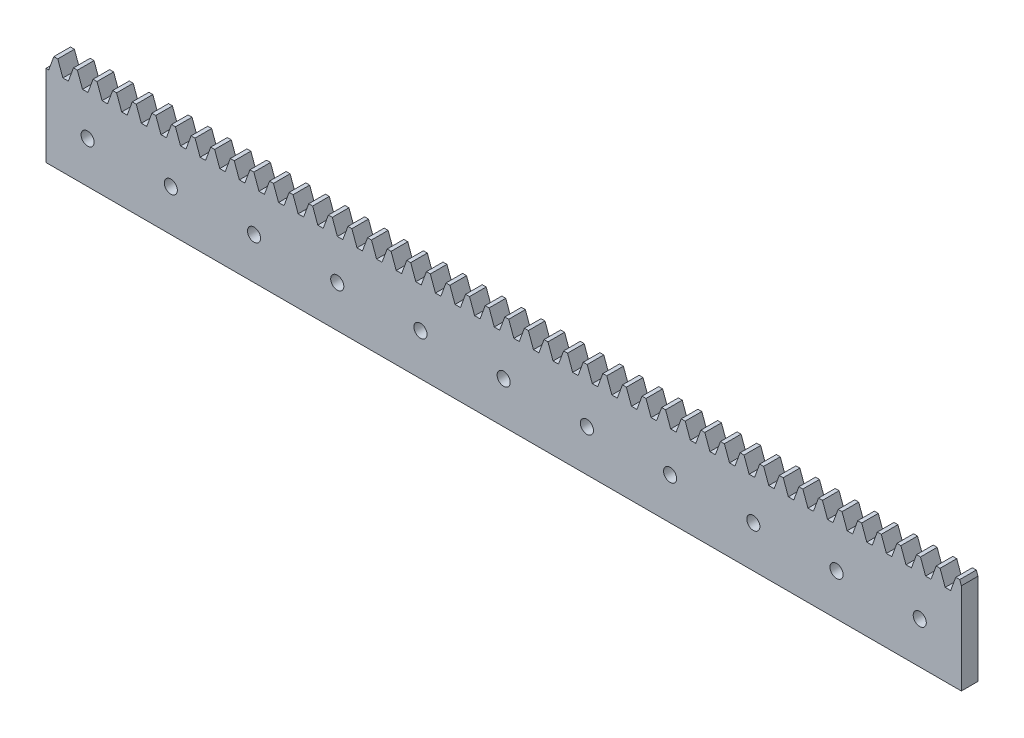
SolidWorks part; units mm, degrees
extrude "Blank" add sketch "BlankSke" against normal blind 4
sketch "BlankSke" plane through (0, 0, 0) normal (0, 0, 1) x (1, 0, 0)
  line L1 (0, 0) -> (660, 0)
  line L2 (0, 0) -> (0, 23)
  line L3 (0, 23) -> (660, 23)
  line L4 (660, 0) -> (660, 23)
  dimension "Length" = 660
ref_plane "Plane1" through (0, 0, 0) normal (0, 0, 1) x (1, 0, 0)
ref_plane "Plane2" through (0, 0, 0) normal (0, 1, 0) x (1, 0, 0)
ref_plane "Plane3" through (0, 0, 0) normal (1, 0, 0) x (0, 0, -1)
other "Configuration Table"
sketch "HoldingSke" plane through (0, 0, 0) normal (0, 1, 0) x (1, 0, 0)
  line L0 (0, 0) -> (0.0928, 0.6602)
  line L1 (-15, 0) -> (100, 0) construction
  line L2 (0, 0) -> (-2.1039, 2.3779)
  line L3 (0, 0) -> (-11.863, 4.5341)
  line L4 (0, 0) -> (-6.8053, 5.3169)
  line L5 (0, 0) -> (-23.7986, -8.8762)
  line L6 (0, 0) -> (-10.5278, -7.1032)
  line L9 (-71.009, 38.7566) -> (549.1882, 264.4899)
  line L10 (-76.2, 3.8779) -> (-54.7, 3.8779)
  line L11 (0, 0) -> (-4, 0)
  line L12 (-76.2, 101.6) -> (-76.147, 101.6)
  line L13 (24.9733, 27.94) -> (52.9518, 28.4284)
  line L14 (24.9733, 27.94) -> (24.9743, 27.94)
  line L15 (24.9733, 27.94) -> (100.4006, 29.5858)
  circle A0 centre (0, 0) radius 19.05
  circle A1 centre (0, 0) radius 10.75
  circle A2 centre (0, 0) radius 12.7
  dimension "Num_teeth" = 142
  dimension "Width" = 4
  dimension "Length" = 660
  dimension "Pitch_height" = 21.5
sketch "TooCutSkeIll" plane through (0, 0, 0) normal (0, 0, 1) x (1, 0, 0)
  line L0 (-1.8687, 22.9605) -> (-0.7447, 19.8724)
  line L1 (-0.3914, 19.625) -> (0.3914, 19.625)
  line L2 (0.7447, 19.8724) -> (1.8687, 22.9605)
  line L3 (660, 23) -> (0, 23) construction
  line L4 (0, 0) -> (0, 64.897) construction
  line L5 (-13.208, 21.5) -> (12.954, 21.5) construction
  line L6 (0, 0) -> (660, 0) construction
  line L7 (1.3371, 21.5) -> (1.3371, 48.7463) construction
  line L8 (-1.3371, 21.5) -> (-1.3371, 48.7463) construction
  line L9 (1.9251, 23) -> (1.9251, 23.0254)
  line L10 (-1.9251, 23) -> (-1.9251, 23.0254)
  line L11 (-1.9251, 23.0254) -> (1.9251, 23.0254)
  arc A0 (0.3914, 19.625) -> (0.7447, 19.8724) centre (0.3914, 20.001) ccw
  arc A1 (-0.7447, 19.8724) -> (-0.3914, 19.625) centre (-0.3914, 20.001) ccw
  arc A2 (1.9251, 23) -> (1.8687, 22.9605) centre (1.9251, 22.94) ccw
  arc A3 (-1.8687, 22.9605) -> (-1.9251, 23) centre (-1.9251, 22.94) ccw
  dimension "Addendum_plus" = 1.5254
  dimension "Pitch_height" = 21.5
  dimension "Pressure_angle" = 20
  dimension "Gap_width" = 2.6742
  dimension "Dedendum" = 1.875
extrude "ToothCutIll" [suppressed] cut sketch "TooCutSkeIll" against normal through all
sketch "TooCutSkeSim" plane through (0, 0, 0) normal (0, 0, 1) x (1, 0, 0)
  line L0 (0.6547, 19.625) -> (-0.6547, 19.625)
  line L1 (1.8923, 23.0254) -> (0.6547, 19.625)
  line L2 (0, 17.4625) -> (0, 53.467) construction
  line L3 (1.8923, 23.0254) -> (-1.8923, 23.0254)
  line L6 (-1.8923, 23.0254) -> (-0.6547, 19.625)
  line L9 (-1.3371, 21.5) -> (1.3371, 21.5) construction
  line L10 (0, 0) -> (660, 0) construction
  line L11 (1.3371, 21.5) -> (1.3371, 53.467) construction
  line L12 (-1.3371, 21.5) -> (-1.3371, 53.467) construction
  dimension "Addendum_plus" = 1.5254
  dimension "Pitch_height" = 21.5
  dimension "Pressure_angle" = 20
  dimension "Gap_width" = 2.6742
  dimension "Dedendum" = 1.875
extrude "ToothCutSim" cut sketch "TooCutSkeSim" against normal through all
pattern_linear "TeethCuts" count 142 spacing 4.7124 along (1, 0, 0) of "ToothCutIll", "ToothCutSim"
sketch "草图2" plane through (0, 0, 0) normal (0, 0, 1) x (1, 0, 0)
  line L0 (660, 0) -> (660, 19.625) construction
  line L2 (0, 0) -> (660, 0) construction
  circle A0 centre (650, 10) radius 1.575
  circle A1 centre (630, 10) radius 1.575
  circle A2 centre (610, 10) radius 1.575
  circle A3 centre (590, 10) radius 1.575
  circle A4 centre (570, 10) radius 1.575
  circle A5 centre (550, 10) radius 1.575
  circle A6 centre (530, 10) radius 1.575
  circle A7 centre (510, 10) radius 1.575
  circle A8 centre (490, 10) radius 1.575
  circle A9 centre (470, 10) radius 1.575
  circle A10 centre (450, 10) radius 1.575
  circle A11 centre (430, 10) radius 1.575
  circle A12 centre (410, 10) radius 1.575
  circle A13 centre (390, 10) radius 1.575
  circle A14 centre (370, 10) radius 1.575
  circle A15 centre (350, 10) radius 1.575
  circle A16 centre (330, 10) radius 1.575
  circle A17 centre (310, 10) radius 1.575
  circle A18 centre (290, 10) radius 1.575
  circle A19 centre (270, 10) radius 1.575
  circle A20 centre (250, 10) radius 1.575
  circle A21 centre (230, 10) radius 1.575
  circle A22 centre (210, 10) radius 1.575
  circle A23 centre (190, 10) radius 1.575
  circle A24 centre (170, 10) radius 1.575
  circle A25 centre (150, 10) radius 1.575
  circle A26 centre (130, 10) radius 1.575
  circle A27 centre (110, 10) radius 1.575
  circle A28 centre (90, 10) radius 1.575
  circle A29 centre (70, 10) radius 1.575
  circle A30 centre (50, 10) radius 1.575
  circle A31 centre (30, 10) radius 1.575
  circle A32 centre (10, 10) radius 1.575
  dimension "D4" = 3.15
  dimension "D1" = 10
  dimension "D3" = 20
  dimension "D5" = 10
  dimension "D2" = 33
extrude "切除-拉伸2" cut sketch "草图2" against normal through all
sketch "草图3" plane through (0, 0, 0) normal (0, 0, 1) x (1, 0, 0)
  line L1 (660, 0) -> (220, 0)
  line L2 (660, 0) -> (660, 65.5478)
  line L3 (660, 65.5478) -> (220, 65.5478)
  line L4 (220, 0) -> (220, 65.5478)
  dimension "D1" = 440
extrude "切除-拉伸3" cut sketch "草图3" against normal through all
equation "' \"Module@HoldingSke\" = 6.35"
equation "' \"Num_teeth@HoldingSke\" = 12"
equation "' \"Ap@HoldingSke\" =  20"
equation "' \"Ap@HoldingSke\" = 20"
equation "' \"Width@HoldingSke\" = 0.25 * 25.4"
equation "' \"Show_teeth@HoldingSke\" = 500"
equation "' \"Backlash@HoldingSke\" = 0.009 * 25.4"
equation "' \"Addendum_fac@HoldingSke\" = 1.0"
equation "' \"Dedendum_fac@HoldingSke\" = 1.25"
equation "' \"Dedendum_add@HoldingSke\" = 0.00005 * 25.4"
equation "' \"Clearance_fac@HoldingSke\" = 0.25"
equation "' \"Pitch_height@HoldingSke\" = 1 * 25.4"
equation "' \"Length@HoldingSke\" = 4.71 * 25.4"
equation "\"Pitch@HoldingSke\" = 1 / \"Module@HoldingSke\""
equation "\"MPH@HoldingSke\" = \"Dedendum_fac@HoldingSke\" / \"Pitch@HoldingSke\" + 2 * \"Dedendum_add@HoldingSke\" + 0.002 * 25.4"
equation "\"MPH@HoldingSke\" = ((sgn( \"MPH@HoldingSke\" - \"Pitch_height@HoldingSke\")+1)*( \"MPH@HoldingSke\" - \"Pitch_height@HoldingSke\"))/2 + \"Pitch_height@HoldingSke\""
equation "\"Blank_height@BlankSke\" = \"Pitch_height@HoldingSke\" + \"Addendum_fac@HoldingSke\"  / \"Pitch@HoldingSke\" "
equation "\"Length@BlankSke\" =  \"Length@HoldingSke\""
equation "\"Face_width@Blank\" = \"Width@HoldingSke\""
equation "\"Pressure_angle@TooCutSkeIll\" = \"Ap@HoldingSke\""
equation "\"Addendum_plus@TooCutSkeIll\" =  \"Addendum_fac@HoldingSke\"  / \"Pitch@HoldingSke\" + 0.001 *25.4"
equation "\"Dedendum@TooCutSkeIll\" = \"Dedendum_fac@HoldingSke\"  / \"Pitch@HoldingSke\""
equation "\"Pitch_height@TooCutSkeIll\" =  \"MPH@HoldingSke\""
equation "\"Gap_width@TooCutSkeIll\" = 3.14159265 / 2 / \"Pitch@HoldingSke\" + 6 * \"Backlash@HoldingSke\""
equation "\"Pressure_angle@TooCutSkeSim\" = \"Ap@HoldingSke\""
equation "\"Addendum_plus@TooCutSkeSim\" =  \"Addendum_fac@HoldingSke\"  / \"Pitch@HoldingSke\" + 0.001 * 25.4"
equation "\"Dedendum@TooCutSkeSim\" = \"Dedendum_fac@HoldingSke\"  / \"Pitch@HoldingSke\""
equation "\"Pitch_height@TooCutSkeSim\" =  \"MPH@HoldingSke\""
equation "\"Gap_width@TooCutSkeSim\" = 3.14159265 / 2 / \"Pitch@HoldingSke\" + 6 * \"Backlash@HoldingSke\""
equation "\"Root_fillet@TooCutSkeIll\" = \"Clearance_fac@HoldingSke\" / \"Pitch@HoldingSke\" + \"Dedendum_add@HoldingSke\""
equation "\"Break_rad@TooCutSkeIll\" = 0.02 / \"Pitch@HoldingSke\" * 2"
equation "\"Linear_pitch@TeethCuts\" = 3.14159265 / \"Pitch@HoldingSke\""
equation "\"Num_teeth@HoldingSke\" = int( ( \"Length@HoldingSke\" + 0 ) / (3.14159265 / \"Pitch@HoldingSke\")) + 0.9999  + 1"
equation " \"Num_teeth@TeethCuts\" = int( \"Show_teeth@HoldingSke\" ) + 1"
equation " \"Num_teeth@TeethCuts\" = ((sgn( \"Num_teeth@TeethCuts\" - \"Num_teeth@HoldingSke\" )-1)*( \"Num_teeth@TeethCuts\" - \"Num_teeth@HoldingSke\" ))/-2+ \"Num_teeth@HoldingSke\""
equation " \"Num_teeth@TeethCuts\" = ((sgn( \"Num_teeth@TeethCuts\" - 2.0)+1)*( \"Num_teeth@TeethCuts\" - 2.0))/2 +2.0"
